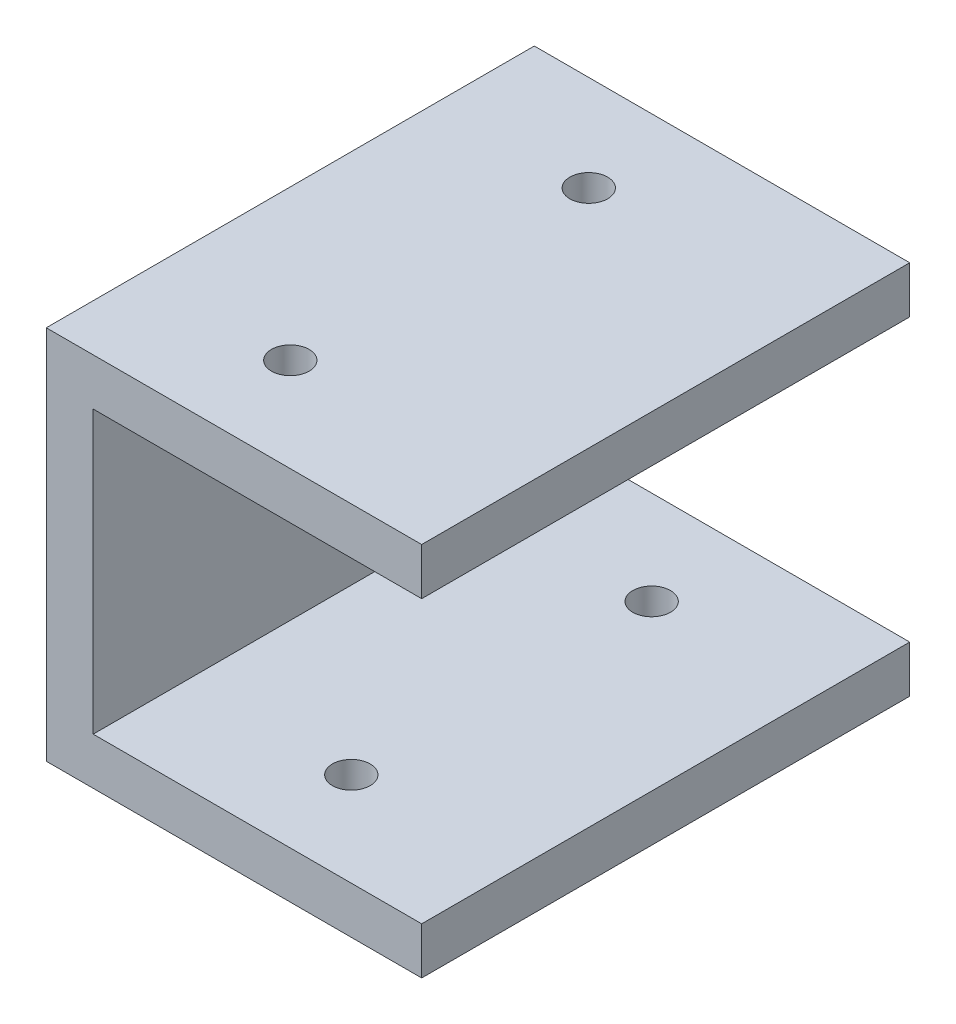
SolidWorks part; units mm, degrees
material "6063-T5"
ref_plane "Front Plane" through (0, 0, 0) normal (0, 0, 1) x (1, 0, 0)
ref_plane "Top Plane" through (0, 0, 0) normal (0, 1, 0) x (1, 0, 0)
ref_plane "Right Plane" through (0, 0, 0) normal (1, 0, 0) x (0, 0, -1)
sketch "Sketch1" plane through (0, 0, 0) normal (0, 0, 1) x (1, 0, 0)
  line L0 (-18.7358, -25.6169) -> (25.7142, -25.6169)
  line L1 (-25.0858, -19.2669) -> (25.7142, -19.2669)
  line L2 (-25.0858, -19.2669) -> (-25.0858, -70.0669)
  line L3 (-25.0858, -70.0669) -> (25.7142, -70.0669)
  line L4 (25.7142, -19.2669) -> (25.7142, -25.6169)
  line L6 (-18.7358, -63.7169) -> (25.7142, -63.7169)
  line L7 (-18.7358, -25.6169) -> (-18.7358, -63.7169)
  line L8 (19.3642, -25.6169) -> (19.3642, -63.7169) construction
  line L9 (-18.7358, -25.6169) -> (19.3642, -25.6169) construction
  line L10 (-18.7358, -63.7169) -> (19.3642, -63.7169) construction
  line L11 (25.7142, -63.7169) -> (25.7142, -70.0669)
  line L12 (25.7142, -19.2669) -> (25.7142, -70.0669) construction
  dimension "D1" = 50.8
  dimension "D2" = 50.8
  dimension "D3" = 6.35
extrude "Boss-Extrude1" add sketch "Sketch1" against normal blind 66.04
hole_wizard "1/4-20 Tapped Hole1" positions "Sketch2" profile "Sketch3" tap size "1/4-20" standard "ANSI Inch" end condition up to next
sketch "Sketch2" plane through (0, -19.2669, 0) normal (0, 1, 0) x (1, 0, 0)
  point P0 (-4.7658, 53.086)
  point P3 (-4.7658, 12.7)
sketch "Sketch3" plane through (-4.7658, -19.2669, -53.086) normal (1, 0, 0) x (0, 0, 1)
  line L0 (0, 0) -> (0, 6.35)
  line L1 (0, 6.35) -> (2.5527, 6.35)
  line L2 (2.5527, 6.35) -> (2.5527, 0)
  line L5 (2.5527, 0) -> (0, 0)
  line L11 (0, -6.35) -> (0, 107.95) construction
  dimension "Thread Major Dia." = 5.1054
  dimension "Thru Tap Drill Depth" = 6.35
hole_wizard "1/4-20 Tapped Hole2" positions "Sketch4" profile "Sketch5" tap size "1/4-20" standard "ANSI Inch" end condition up to next
sketch "Sketch4" plane through (0, -70.0669, 0) normal (0, -1, 0) x (-1, 0, 0)
  line L0 (-3.4892, 66.04) -> (-3.4892, 0) construction
  line L1 (25.0858, 66.04) -> (-25.7142, 66.04) construction
  line L2 (25.0858, 0) -> (-25.7142, 0) construction
  line L4 (-25.7142, 66.04) -> (-25.7142, 0) construction
  point P15 (-3.4892, 53.34)
  point P17 (-3.4892, 12.7)
  dimension "D1" = 22.225
  dimension "D2" = 12.7
  dimension "D3" = 12.7
sketch "Sketch5" plane through (3.4892, -70.0669, -12.7) normal (1, 0, 0) x (0, 0, -1)
  line L0 (0, 0) -> (0, 6.35)
  line L1 (0, 6.35) -> (2.5527, 6.35)
  line L2 (2.5527, 6.35) -> (2.5527, 0)
  line L5 (2.5527, 0) -> (0, 0)
  line L11 (0, -6.35) -> (0, 107.95) construction
  dimension "Thru Tap Drill Dia." = 5.1054
  dimension "Thru Tap Drill Depth" = 6.35
cosmetic thread "Hole Thread1"
cosmetic thread "Hole Thread2"
